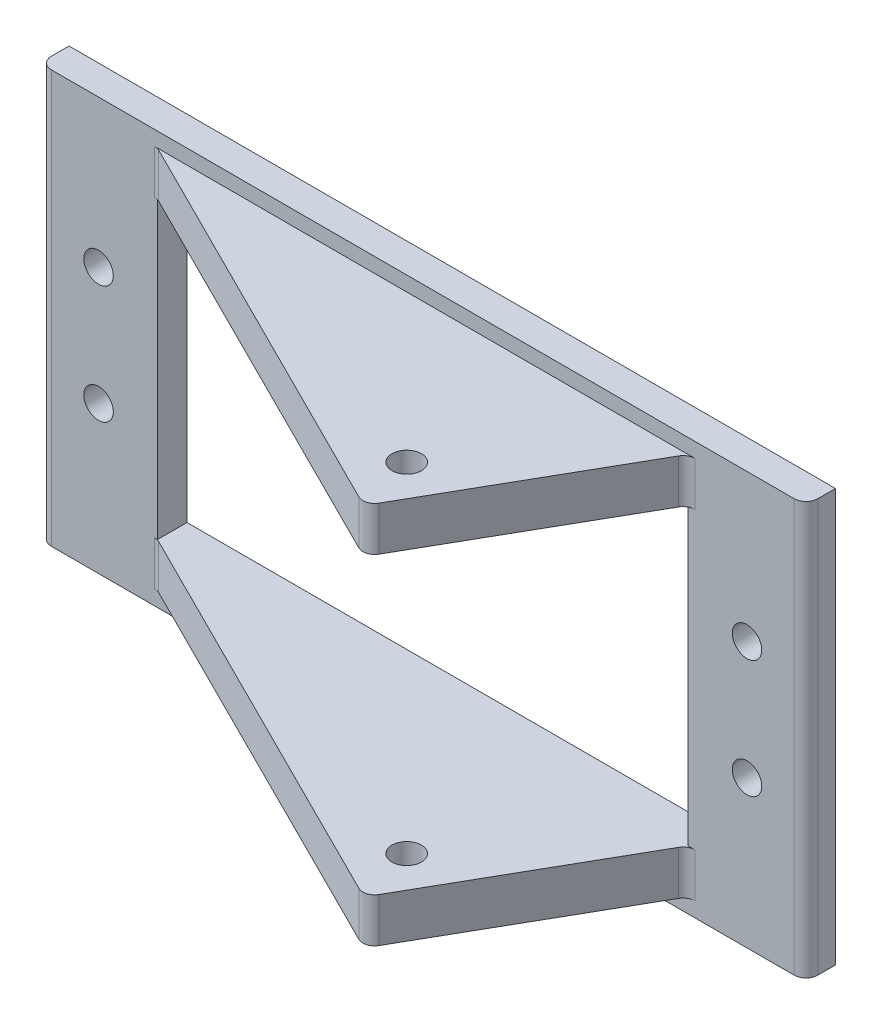
SolidWorks part; units mm, degrees
material "6061-T6 (SS)"
ref_plane "Front Plane" through (0, 0, 0) normal (0, 0, 1) x (1, 0, 0)
ref_plane "Top Plane" through (0, 0, 0) normal (0, 1, 0) x (1, 0, 0)
ref_plane "Right Plane" through (0, 0, 0) normal (1, 0, 0) x (0, 0, -1)
sketch "Sketch1" plane through (0, 0, 0) normal (0, 0, 1) x (1, 0, 0)
  line L1 (-82.55, 44.45) -> (82.55, 44.45)
  line L2 (-82.55, 44.45) -> (-82.55, -44.45)
  line L3 (-82.55, -44.45) -> (82.55, -44.45)
  line L4 (82.55, 44.45) -> (82.55, -44.45)
  line L5 (-82.55, 44.45) -> (82.55, -44.45) construction
  line L6 (-82.55, -44.45) -> (82.55, 44.45) construction
  point P0 (0, 0)
  dimension "D1" = 165.1
  dimension "D2" = 88.9
extrude "Boss-Extrude1" add sketch "Sketch1" along normal blind 50.8
sketch "Sketch2" plane through (0, 0, 50.8) normal (0, 0, 1) x (1, 0, 0)
  line L0 (-82.55, 0) -> (82.55, 0) construction
  line L1 (82.55, -44.45) -> (82.55, 44.45) construction
  line L2 (0, 0) -> (0, -31.75) construction
  line L3 (-57.15, 31.75) -> (57.15, 31.75)
  line L4 (-57.15, 31.75) -> (-57.15, -31.75)
  line L5 (-57.15, -31.75) -> (57.15, -31.75)
  line L6 (57.15, 31.75) -> (57.15, -31.75)
  line L7 (-57.15, 31.75) -> (57.15, -31.75) construction
  line L8 (-57.15, -31.75) -> (57.15, 31.75) construction
  circle A0 centre (-69.85, 12.7) radius 3.175
  circle A1 centre (-69.85, -12.7) radius 3.175
  circle A2 centre (69.85, -12.7) radius 3.175
  circle A3 centre (69.85, 12.7) radius 3.175
  point P0 (0, 0)
  point P6 (0, 0)
  dimension "D3" = 6.35
  dimension "D1" = 114.3
  dimension "D2" = 63.5
  dimension "D4" = 12.7
  dimension "D5" = 12.7
extrude "Cut-Extrude1" cut sketch "Sketch2" against normal through all
ref_plane "Plane1" through (0, -40.64, 0) normal (0, -1, 0) x (-1, 0, 0)
ref_plane "Plane2" through (0, 1.905, 0) normal (0, -1, 0) x (-1, 0, 0)
ref_plane "Plane3" through (0, 40.64, 0) normal (0, 1, 0) x (1, 0, 0)
sketch "Sketch3" plane through (0, 0, 0) normal (0, 0, -1) x (-1, 0, 0)
  line L1 (-57.15, 38.1) -> (57.15, 38.1)
  line L2 (-57.15, 38.1) -> (-57.15, -38.1)
  line L3 (-57.15, -38.1) -> (57.15, -38.1)
  line L4 (57.15, 38.1) -> (57.15, -38.1)
  line L5 (-57.15, 38.1) -> (57.15, -38.1) construction
  line L6 (-57.15, -38.1) -> (57.15, 38.1) construction
  point P0 (0, 0)
  dimension "D1" = 76.2
sketch "Sketch4" plane through (0, 0, 50.8) normal (0, 0, 1) x (1, 0, 0)
  line L1 (82.55, 44.45) -> (-82.55, 44.45)
  line L2 (82.55, 44.45) -> (82.55, -44.45)
  line L3 (82.55, -44.45) -> (-82.55, -44.45)
  line L4 (-82.55, 44.45) -> (-82.55, -44.45)
  line L5 (82.55, 44.45) -> (-82.55, -44.45) construction
  line L6 (82.55, -44.45) -> (-82.55, 44.45) construction
  line L7 (57.15, 41.275) -> (-57.15, 41.275)
  line L8 (57.15, 41.275) -> (57.15, -41.275)
  line L9 (57.15, -41.275) -> (-57.15, -41.275)
  line L10 (-57.15, 41.275) -> (-57.15, -41.275)
  line L11 (57.15, 41.275) -> (-57.15, -41.275) construction
  line L12 (57.15, -41.275) -> (-57.15, 41.275) construction
  point P0 (0, 0)
  point P7 (0, 0)
  dimension "D1" = 82.55
  dimension "D2" = 114.3
extrude "Cut-Extrude2" cut sketch "Sketch4" against normal blind 44.45
sketch "Sketch5" plane through (0, -41.275, 0) normal (0, -1, 0) x (1, 0, 0)
  line L0 (0, 0) -> (31.75, 0) construction
  line L1 (-82.55, 0) -> (82.55, 0) construction
  line L2 (31.75, 35.4766) -> (31.75, 50.8) construction
  line L3 (31.75, 0) -> (31.75, 6.35) construction
  line L4 (-57.15, 50.8) -> (57.15, 50.8) construction
  line L6 (-57.15, 0) -> (31.75, 0) construction
  line L7 (57.15, 6.35) -> (31.75, 50.8)
  line L8 (31.75, 50.8) -> (-57.15, 6.35)
  line L12 (27.1461, 33.9189) -> (31.75, 50.8) construction
  line L13 (57.15, 6.35) -> (57.15, 50.8)
  line L14 (57.15, 50.8) -> (-57.15, 50.8)
  line L15 (-57.15, 50.8) -> (-57.15, 6.35)
  circle A0 centre (28.2864, 38.1) radius 3.175
  line M7 (57.15, 50.8) -> (-57.15, 50.8)
  line M8 (-57.15, 50.8) -> (-57.15, 6.35)
  line M10 (57.15, 6.35) -> (57.15, 50.8)
  dimension "D6" = 6.35
  dimension "D1" = 31.75
  dimension "D2" = 88.9
  dimension "D3" = 45
  dimension "D4" = 12.7
extrude "Cut-Extrude4" cut sketch "Sketch5" against normal through all contours L8 M7 M8 | L7 M10 M7 | A0 region at (-27.5167, -41.275, 35.9833) region at (48.6833, -41.275, 35.9833) region at (28.2864, -41.275, 38.1)
fillet "Fillet2" radius 2.54 8 edges at (82.55, 0, 6.35) (57.15, 36.5125, 6.35) (57.15, -36.5125, 6.35) (31.75, -36.5125, 50.8) (31.75, 36.5125, 50.8) (-57.15, -36.5125, 6.35) (-57.15, 36.5125, 6.35) (-82.55, 0, 6.35)
